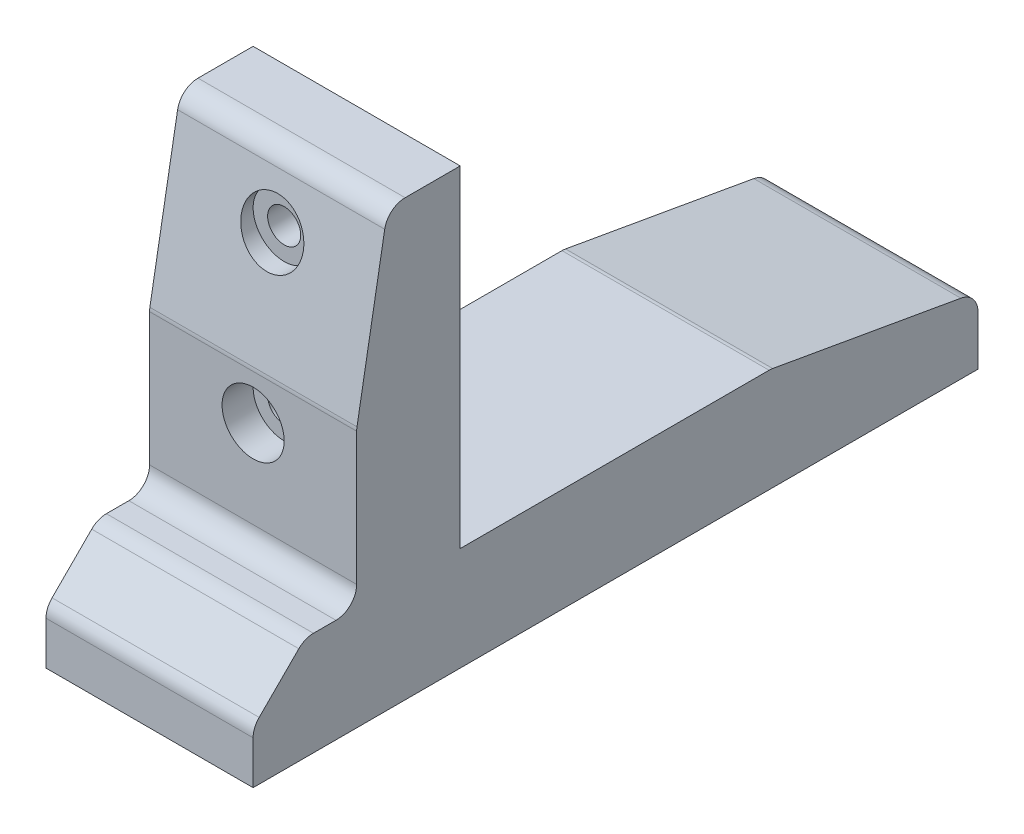
SolidWorks part; units mm, degrees
ref_plane "Front Plane" through (0, 0, 0) normal (0, 0, 1) x (1, 0, 0)
ref_plane "Top Plane" through (0, 0, 0) normal (0, 1, 0) x (1, 0, 0)
ref_plane "Right Plane" through (0, 0, 0) normal (1, 0, 0) x (0, 0, -1)
ref_plane "Plane1" through (37.1227, 0, 0) normal (1, 0, 0) x (0, 0, -1)
sketch "Sketch3" plane through (37.1227, 0, 0) normal (1, 0, 0) x (0, 0, -1)
  line L0 (0, -48.9607) -> (0, 81.0393) construction
  line L1 (0, -37.4607) -> (-10, -37.4607)
  line L2 (0, -37.4607) -> (0, -69.4607)
  line L3 (0, -69.4607) -> (-10, -69.4607)
  line L4 (-10, -37.4607) -> (-10, -69.4607)
  line L5 (19, -68.9607) -> (0, -68.9607) construction
  line L6 (-20, -79.4607) -> (50, -79.4607)
  line L7 (-20, -79.4607) -> (-20, -69.4607)
  line L8 (-20, -69.4607) -> (50, -69.4607)
  line L9 (50, -79.4607) -> (50, -69.4607)
  dimension "D1" = 0.5
  dimension "D2" = 10
  dimension "D3" = 32
  dimension "D4" = 50
  dimension "D5" = 10
  dimension "D6" = 10
extrude "Boss-Extrude1" add sketch "Sketch3" along normal mid plane 20 contours L6 L9 L8 L3 L7 | L1 L4 L3 L2 region at (37.1227, -53.4607, 5) region at (37.1227, -74.4607, -15)
sketch "Sketch4" plane through (0, 0, 0) normal (0, 0, -1) x (-1, 0, 0)
  circle A0 centre (-37.1227, -58.9607) radius 1.6 construction
  circle A1 centre (-37.1227, -43.9607) radius 1.6 construction
  circle A2 centre (-37.1227, -58.9607) radius 1.6
  circle A3 centre (-37.1227, -43.9607) radius 1.6
  circle A4 centre (-37.1227, -43.9607) radius 3
  circle A5 centre (-37.1227, -58.9607) radius 3
  dimension "D1" = 6
extrude "Cut-Extrude1" cut sketch "Sketch4" against normal through all contours A3 | A2 region at (37.1227, -58.9607, 0) region at (37.1227, -43.9607, 0)
extrude "Cut-Extrude2" cut sketch "Sketch4<3>" along normal blind 3 from surface contours A4 A3 | A5 A2 region at (40.0378, -43.9607, 0) region at (40.0378, -58.9607, 0) starting at face at (37.1227, -42.3607, 10)
sketch "Sketch4<3>" plane through (0, 0, 0) normal (0, 0, -1) x (-1, 0, 0) same geometry as "Sketch4"
chamfer "Chamfer1" distance 20 angle 10 1 edges at (37.1227, -69.4607, -50) first distance on face at (37.1227, -69.4607, -25)
chamfer "Chamfer2" distance 5 angle 45 1 edges at (37.1227, -69.4607, 20)
chamfer "Chamfer3" distance 3 angle 80 1 edges at (37.1227, -37.4607, 10) first distance on face at (37.1227, -37.4607, 5)
fillet "Fillet1" radius 2 7 edges at (37.1227, -37.4607, 7) (37.1227, -54.4745, 10) (37.1227, -69.4607, 10) (37.1227, -69.4607, 15) (37.1227, -74.4607, 20) (37.1227, -69.4607, -30) (37.1227, -72.9872, -50)
